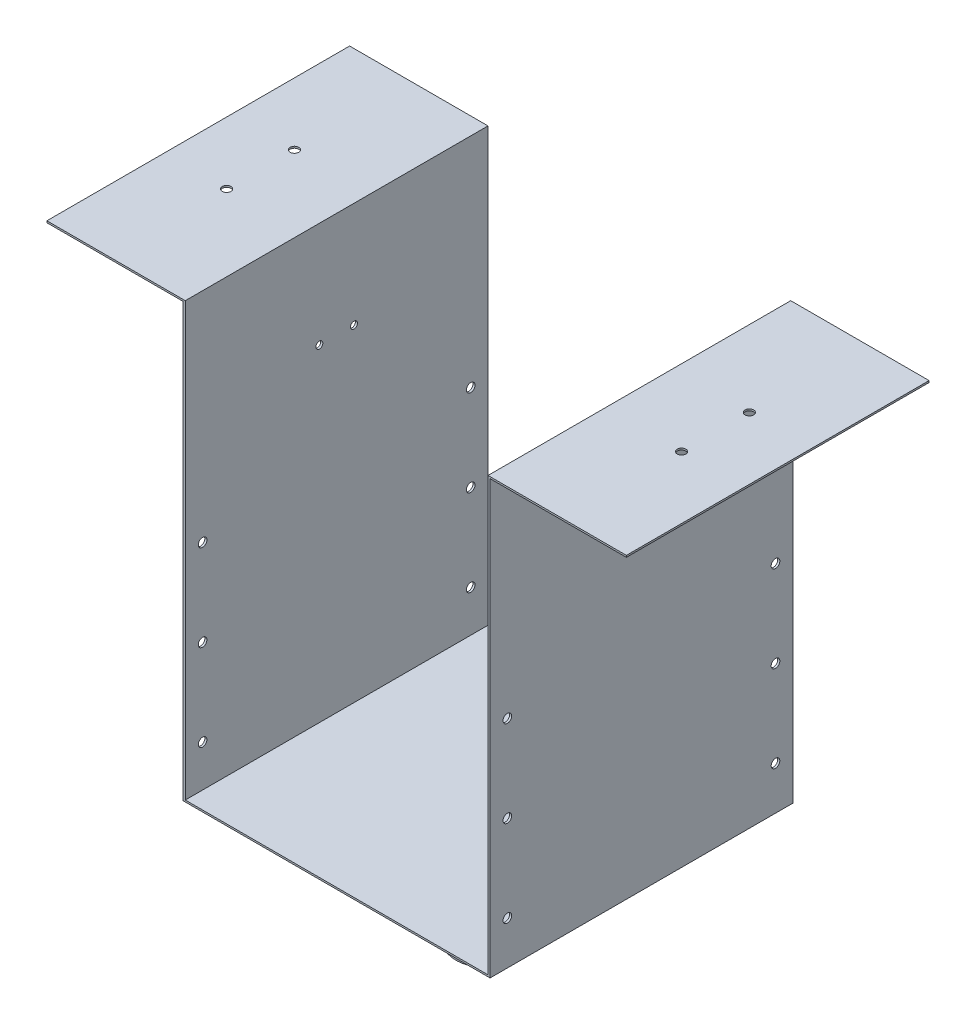
SolidWorks part; units mm, degrees
ref_plane "Front Plane" through (0, 0, 0) normal (0, 0, 1) x (1, 0, 0)
ref_plane "Top Plane" through (0, 0, 0) normal (0, 1, 0) x (1, 0, 0)
ref_plane "Right Plane" through (0, 0, 0) normal (1, 0, 0) x (0, 0, -1)
sketch "Sketch1" plane through (0, 0, 0) normal (0, 1, 0) x (1, 0, 0)
  line L1 (-87.5, -87.5) -> (87.5, -87.5)
  line L2 (-87.5, -87.5) -> (-87.5, 87.5)
  line L3 (-87.5, 87.5) -> (87.5, 87.5)
  line L4 (87.5, -87.5) -> (87.5, 87.5)
  line L5 (-87.5, -87.5) -> (87.5, 87.5) construction
  line L6 (-87.5, 87.5) -> (87.5, -87.5) construction
  point P0 (0, 0)
  dimension "D1" = 175
extrude "Boss-Extrude1" add sketch "Sketch1" along normal blind 1
sketch "Sketch2" plane through (0, 0, 0) normal (0, -1, 0) x (1, 0, 0)
  line L0 (0, -87.5) -> (0, 87.5) construction
  line L1 (-87.5, -87.5) -> (-88.7, -87.5)
  line L2 (-87.5, -87.5) -> (-87.5, 87.5)
  line L3 (-87.5, 87.5) -> (-88.7, 87.5)
  line L4 (-88.7, -87.5) -> (-88.7, 87.5)
  line L5 (87.5, -87.5) -> (-87.5, -87.5) construction
  line L6 (-87.5, 87.5) -> (87.5, 87.5) construction
  line L7 (88.7, -87.5) -> (88.7, 87.5)
  line L8 (87.5, 87.5) -> (88.7, 87.5)
  line L9 (87.5, -87.5) -> (87.5, 87.5)
  line L10 (87.5, -87.5) -> (88.7, -87.5)
  dimension "D1" = 1.2
extrude "Boss-Extrude2" add sketch "Sketch2" against normal blind 250
sketch "Sketch3" plane through (0, 250, 0) normal (0, 1, 0) x (1, 0, 0)
  line L0 (0, 87.5) -> (0, -87.5) construction
  line L1 (-87.5, 87.5) -> (-167.5, 87.5)
  line L2 (-87.5, 87.5) -> (-87.5, -87.5)
  line L3 (-87.5, -87.5) -> (-167.5, -87.5)
  line L4 (-167.5, 87.5) -> (-167.5, -87.5)
  line L5 (87.5, 87.5) -> (-87.5, 87.5) construction
  line L6 (-87.5, -87.5) -> (87.5, -87.5) construction
  line L7 (167.5, 87.5) -> (167.5, -87.5)
  line L8 (87.5, -87.5) -> (167.5, -87.5)
  line L9 (87.5, 87.5) -> (87.5, -87.5)
  line L10 (87.5, 87.5) -> (167.5, 87.5)
  dimension "D1" = 80
extrude "Boss-Extrude3" add sketch "Sketch3" along normal blind 1
sketch "Sketch4" plane through (0, 251, 0) normal (0, 1, 0) x (1, 0, 0)
  line L0 (87.5, 0) -> (131.5, 0) construction
  line L1 (87.5, 0) -> (167.5, 0) construction
  line L2 (131.5, 0) -> (131.5, 19.6) construction
  line L3 (0, 87.5) -> (0, -87.5) construction
  line L4 (87.5, 87.5) -> (-87.5, 87.5) construction
  line L5 (-87.5, -87.5) -> (87.5, -87.5) construction
  line L6 (-131.5, 0) -> (-131.5, 19.6) construction
  line L7 (-87.5, 0) -> (-131.5, 0) construction
  circle A1 centre (131.5, 19.6) radius 2.5
  circle A2 centre (131.5, -19.6) radius 2.5
  circle A3 centre (-131.5, -19.6) radius 2.5
  circle A4 centre (-131.5, 19.6) radius 2.5
  dimension "D3" = 5
  dimension "D1" = 44
  dimension "D2" = 19.6
extrude "Cut-Extrude1" cut sketch "Sketch4" against normal blind 10
sketch "Sketch5" plane through (-88.7, 0, 0) normal (-1, 0, 0) x (0, 0, 1)
  line L0 (-87.5, 207.5) -> (87.5, 207.5) construction
  line L1 (-87.5, 250) -> (-87.5, 0) construction
  line L2 (87.5, 250) -> (87.5, 0) construction
  line L3 (-87.5, 177.5) -> (87.5, 177.5) construction
  line L4 (87.5, 250) -> (-87.5, 250) construction
  dimension "D1" = 42.5
  dimension "D2" = 30
sketch "Sketch6" plane through (88.7, 0, 0) normal (1, 0, 0) x (0, 0, -1)
  line L0 (87.5, 25) -> (77.5, 25) construction
  line L1 (87.5, 250) -> (87.5, 0) construction
  line L2 (87.5, 0) -> (-87.5, 0) construction
  line L3 (0, 0) -> (0, 250) construction
  line L4 (87.5, 250) -> (-87.5, 250) construction
  circle A0 centre (77.5, 25) radius 2.5
  circle A1 centre (77.5, 75) radius 2.5
  circle A2 centre (77.5, 125) radius 2.5
  circle A3 centre (-77.5, 125) radius 2.5
  circle A4 centre (-77.5, 75) radius 2.5
  circle A5 centre (-77.5, 25) radius 2.5
  circle A6 centre (-10, 190) radius 2
  circle A7 centre (10, 190) radius 2
  point P21 (0, 0)
  dimension "D2" = 5
  dimension "D5" = 4
  dimension "D1" = 25
  dimension "D4" = 10
  dimension "D6" = 10
  dimension "D7" = 60
  dimension "D3" = 3
extrude "Cut-Extrude2" cut sketch "Sketch6" against normal blind 300
sketch "Sketch7" plane through (0, 0, 0) normal (0, -1, 0) x (1, 0, 0)
  circle A0 centre (0, 0) radius 18.5
  circle A1 centre (0, 0) radius 12.5
  dimension "D1" = 37
  dimension "D2" = 25
extrude "Boss-Extrude4" add sketch "Sketch7" along normal blind 70
